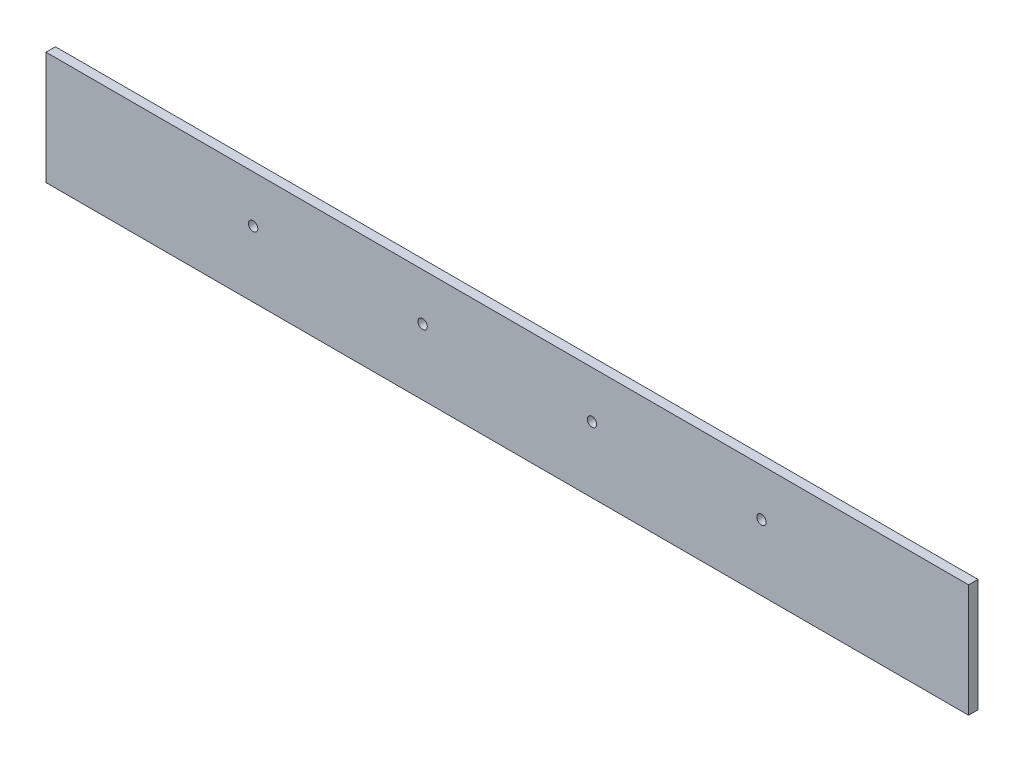
SolidWorks part; units mm, degrees
material "6061 Alloy"
ref_plane "Front Plane" through (0, 0, 0) normal (0, 0, 1) x (1, 0, 0)
ref_plane "Top Plane" through (0, 0, 0) normal (0, 1, 0) x (1, 0, 0)
ref_plane "Right Plane" through (0, 0, 0) normal (1, 0, 0) x (0, 0, -1)
sketch "Sketch1" plane through (0, 0, 457.2) normal (0, 0, 1) x (1, 0, 0)
  line L0 (311.15, 0) -> (311.15, 571.5) construction
  line L1 (-311.15, 609.6) -> (311.15, 609.6)
  line L2 (-311.15, 609.6) -> (-311.15, 533.4)
  line L3 (-311.15, 533.4) -> (311.15, 533.4)
  line L4 (311.15, 609.6) -> (311.15, 533.4)
  line L6 (311.15, 114.3) -> (-311.15, 114.3) construction
  dimension "D1" = 419.1
extrude "Boss-Extrude1" add sketch "Sketch1" along normal blind 6.35
sketch "Sketch2" plane through (0, 0, 463.55) normal (0, 0, 1) x (1, 0, 0)
  point P0 (171.45, 577.85)
hole_wizard "1/4 (0.25) Diameter Hole1" positions "Sketch2" profile "Sketch3" hole size "1/4" standard "ANSI Inch" end condition through all
sketch "Sketch3" plane through (171.45, 577.85, 463.55) normal (1, 0, 0) x (0, -1, 0)
  line L0 (0, 0) -> (0, 6.35)
  line L1 (0, 6.35) -> (3.175, 6.35)
  line L2 (3.175, 6.35) -> (3.175, 0)
  line L5 (3.175, 0) -> (0, 0)
  line L11 (0, -6.35) -> (0, 107.95) construction
  dimension "Thru Hole Dia." = 6.35
  dimension "Thru Hole Depth" = 6.35
pattern_linear "LPattern1" count 4 spacing 114.3 along (-1, 0, 0) of "1/4 (0.25) Diameter Hole1"
